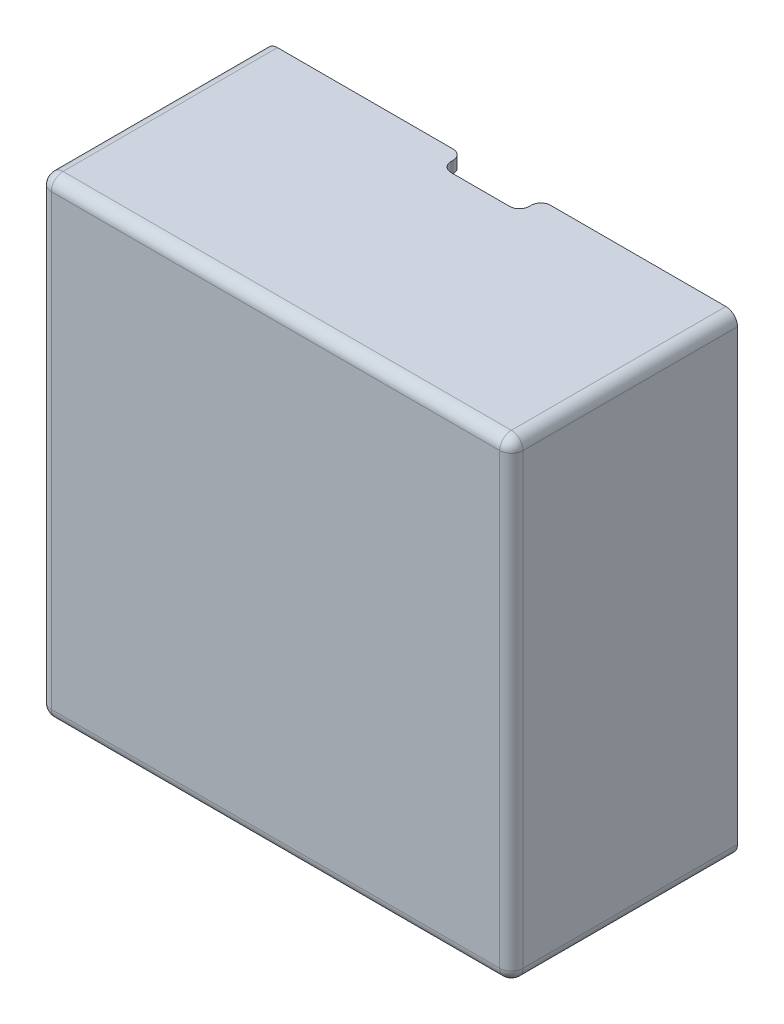
SolidWorks part; units mm, degrees
ref_plane "Front Plane" through (0, 0, 0) normal (0, 0, 1) x (1, 0, 0)
ref_plane "Top Plane" through (0, 0, 0) normal (0, 1, 0) x (1, 0, 0)
ref_plane "Right Plane" through (0, 0, 0) normal (1, 0, 0) x (0, 0, -1)
sketch "Sketch1" plane through (0, 0, 0) normal (0, 0, 1) x (1, 0, 0)
  line L1 (60.5, 60.5) -> (-60.5, 60.5)
  line L2 (60.5, 60.5) -> (60.5, -60.5)
  line L3 (60.5, -60.5) -> (-60.5, -60.5)
  line L4 (-60.5, 60.5) -> (-60.5, -60.5)
  line L5 (60.5, 60.5) -> (-60.5, -60.5) construction
  line L6 (60.5, -60.5) -> (-60.5, 60.5) construction
  line L7 (57.5, 57.5) -> (-57.5, 57.5)
  line L8 (57.5, 57.5) -> (57.5, -57.5)
  line L9 (57.5, -57.5) -> (-57.5, -57.5)
  line L10 (-57.5, 57.5) -> (-57.5, -57.5)
  line L11 (57.5, 57.5) -> (-57.5, -57.5) construction
  line L12 (57.5, -57.5) -> (-57.5, 57.5) construction
  point P0 (0, 0)
  point P6 (0, 0)
  dimension "D1" = 121
  dimension "D2" = 121
  dimension "D3" = 115
  dimension "D4" = 115
extrude "Boss-Extrude1" add sketch "Sketch1" along normal blind 55
sketch "Sketch2" plane through (0, 0, 55) normal (0, 0, 1) x (1, 0, 0)
  line L1 (60.5, -60.5) -> (-60.5, -60.5)
  line L2 (60.5, -60.5) -> (60.5, 60.5)
  line L3 (60.5, 60.5) -> (-60.5, 60.5)
  line L4 (-60.5, -60.5) -> (-60.5, 60.5)
  line L5 (60.5, -60.5) -> (-60.5, 60.5) construction
  line L6 (60.5, 60.5) -> (-60.5, -60.5) construction
  point P0 (0, 0)
extrude "Boss-Extrude2" add sketch "Sketch2" along normal blind 3
fillet "Fillet1" radius 3 8 edges at (0, -57.5, 55) (57.5, 0, 55) (0, 57.5, 55) (-57.5, 0, 55) (-57.5, 57.5, 27.5) (-57.5, -57.5, 27.5) (57.5, -57.5, 27.5) (57.5, 57.5, 27.5)
fillet "Fillet2" radius 3 8 edges at (0, 60.5, 58) (60.5, 0, 58) (0, -60.5, 58) (-60.5, 0, 58) (60.5, -60.5, 29) (-60.5, -60.5, 29) (-60.5, 60.5, 29) (60.5, 60.5, 29)
sketch "Sketch3" plane through (0, -60.5, 0) normal (0, -1, 0) x (1, 0, 0)
  line L1 (10.0543, -4.504) -> (-9.9457, -4.504)
  line L2 (10.0543, -4.504) -> (10.0543, 5.496)
  line L3 (10.0543, 5.496) -> (-9.9457, 5.496)
  line L4 (-9.9457, -4.504) -> (-9.9457, 5.496)
  line L5 (10.0543, -4.504) -> (-9.9457, 5.496) construction
  line L6 (10.0543, 5.496) -> (-9.9457, -4.504) construction
  dimension "D1" = 10
  dimension "D2" = 20
extrude "Cut-Extrude1" cut sketch "Sketch3" against normal blind 177
fillet "Fillet3" radius 2.5 4 edges at (-9.9457, -59, 5.496) (10.0543, -59, 5.496) (10.0543, -59, 0) (-9.9457, -59, 0)
fillet "Fillet4" radius 2.5 4 edges at (-9.9457, 59, 5.496) (-9.9457, 59, 0) (10.0543, 59, 5.496) (10.0543, 59, 0)
